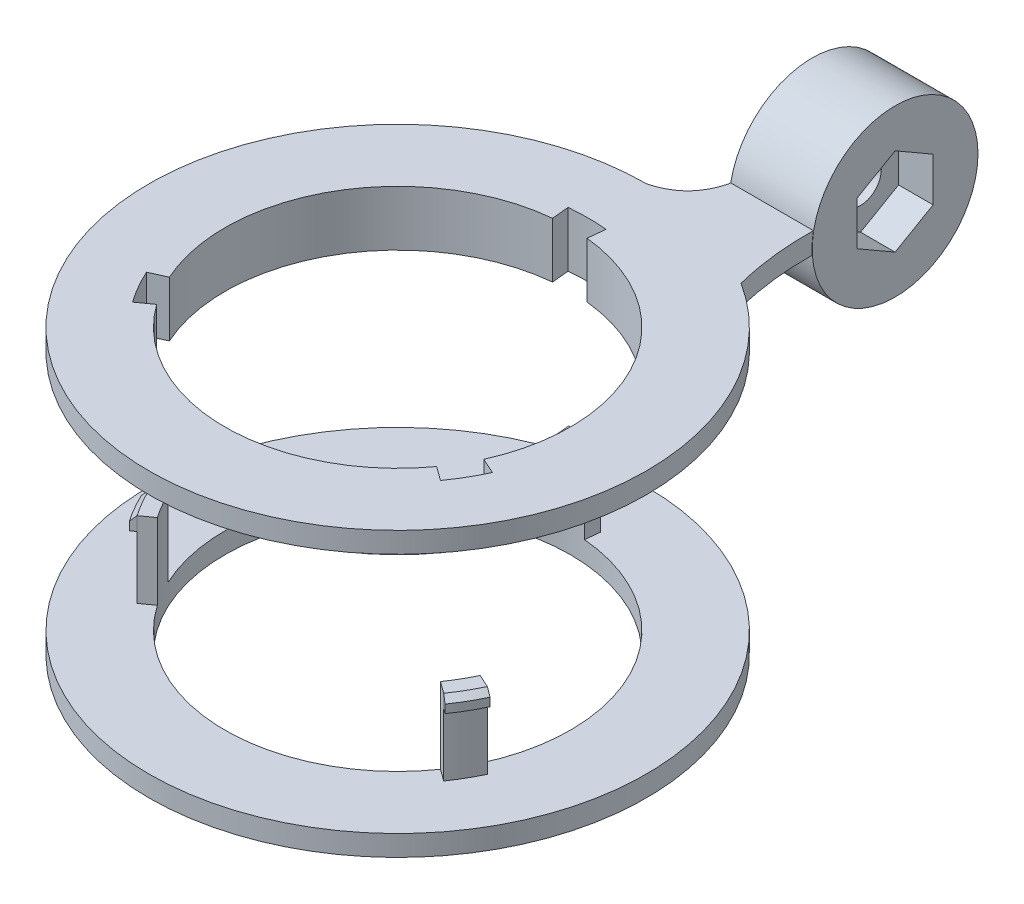
SolidWorks part; units mm, degrees
ref_plane "Plano frontal" through (0, 0, 0) normal (0, 0, 1) x (1, 0, 0)
ref_plane "Plano superior" through (0, 0, 0) normal (0, 1, 0) x (1, 0, 0)
ref_plane "Plano direito" through (0, 0, 0) normal (1, 0, 0) x (0, 0, -1)
ref_plane "Plano24" through (10, 0, 0) normal (1, 0, 0) x (0, 0, -1)
sketch "Esboço120" plane through (10, 0, 0) normal (1, 0, 0) x (0, 0, -1)
  line L6 (-78.5, 184.9522) -> (-73.5, 176.2919)
  line L7 (-78.5, 176.2919) -> (-73.5, 184.9522)
  line L8 (-80.3301, 178.1221) -> (-71.6699, 183.1221)
  line L9 (-81, 180.6221) -> (-71, 180.6221)
  line L10 (-71.6699, 178.1221) -> (-80.3301, 183.1221)
  line L11 (-76, 185.6221) -> (-76, 175.6221)
  circle A0 centre (-76, 180.6221) radius 6
  circle A2 centre (-76, 180.6221) radius 1.5
  circle A4 centre (-76, 180.6221) radius 5
  dimension "D3" = 1
extrude "Ressalto-extrusão39" add sketch "Esboço120" along normal blind 6 separate body contours A0
extrude "Corte-Extrusão-Fina1" cut sketch "Esboço120<3>" along normal blind 0.4 thin contours L9 | L10 | L6 | L11 | L7 | L8 thin type mid plane wall 0.75
sketch "Esboço120<3>" plane through (10, 0, 0) normal (1, 0, 0) x (0, 0, -1) same geometry as "Esboço120"
extrude "Corte-extrusão49" cut sketch "Esboço120<4>" along normal up to next contours A2
sketch "Esboço120<4>" plane through (10, 0, 0) normal (1, 0, 0) x (0, 0, -1) same geometry as "Esboço120"
sketch "Esboço121" plane through (16, 0, 0) normal (1, 0, 0) x (0, 0, -1)
  line L1 (-76, 183.7975) -> (-78.75, 182.2098)
  line L2 (-78.75, 182.2098) -> (-78.75, 179.0343)
  line L3 (-78.75, 179.0343) -> (-76, 177.4466)
  line L4 (-76, 177.4466) -> (-73.25, 179.0343)
  line L5 (-73.25, 179.0343) -> (-73.25, 182.2098)
  line L6 (-73.25, 182.2098) -> (-76, 183.7975)
  circle A0 centre (-76, 180.6221) radius 2.75 construction
  dimension "D1" = 5.5
extrude "Corte-extrusão50" cut sketch "Esboço121" against normal blind 2.5 contours L1 L2 L3 L4 L5 L6
ref_plane "Plao25" through (0, 180.2338, 0) normal (0, 1, 0) x (1, 0, 0)
sketch "Esboço122" plane through (0, 180.2338, 0) normal (0, 1, 0) x (1, 0, 0)
  line L0 (10, -82) -> (10, -81.5)
  line L1 (10, -82) -> (7, -82) construction
  line L2 (7, -82) -> (7, -85) construction
  line L3 (10, -81.5) -> (16, -81.5)
  line L4 (8.2693, -90.5646) -> (8.3962, -89.3211)
  line L5 (7, -85) -> (7, -93) construction
  line L6 (5.7703, -90.5606) -> (5.6474, -89.3167)
  line L7 (18.3876, -108.1548) -> (19.5264, -108.6703)
  line L8 (17.1347, -110.3169) -> (18.1482, -111.0486)
  line L9 (-3.158, -110.2846) -> (-4.1738, -111.0131)
  line L10 (-4.404, -108.1185) -> (-5.5444, -108.6303)
  circle A0 centre (7, -103) radius 18
  circle A1 centre (7, -103) radius 14.5
  circle A2 centre (7, -103) radius 15 construction
  circle A3 centre (7, -103) radius 17 construction
  circle A4 centre (7, -103) radius 12.5
  arc A5 (8.3962, -89.3211) -> (5.6474, -89.3167) centre (7, -103) ccw
  arc A6 (18.1482, -111.0486) -> (19.5264, -108.6703) centre (7, -103) ccw
  arc A7 (-5.5444, -108.6303) -> (-4.1738, -111.0131) centre (7, -103) ccw
  spline S0 degree 2 poles (10, -82) (9.3918, -84.3997) (7, -85) knots 0 0 0 1 1 1
  spline S1 degree 2 poles (16, -81.5) (15.8701, -84.6924) (16.668, -87.8168) knots 0 0 0 1 1 1
  point P3 (10, -82)
  point P35 (7, -103)
  dimension "D2" = 3
  dimension "D3" = 36
  dimension "D5" = 29
  dimension "D8" = 30
  dimension "D11" = 1.25
  dimension "D12" = 3
  dimension "D1" = 3
  dimension "D7" = 0.5
  dimension "D4" = 3.5
  dimension "D6" = 0.5
  dimension "D9" = 2
  dimension "D10" = 2
extrude "Ressalto-extrusão40" add sketch "Esboço122" along normal blind 1.5 contours S1 L3 L0 S0 A0 | A0 A1 | A1 A4 region at (12.9495, 180.2338, 83.9786) region at (11.8926, 180.2338, 86.2073) region at (-7.0899, 180.2338, 103)
extrude "Ressalto-extrusão41" add sketch "Esboço122<12>" against normal blind 2.5 contours A1 A4 region at (-7.0899, 180.2338, 103)
sketch "Esboço122<12>" plane through (0, 180.2338, 0) normal (0, 1, 0) x (1, 0, 0) same geometry as "Esboço122"
ref_plane "Plano25" through (0, 162.7338, 0) normal (0, -1, 0) x (-1, 0, 0)
sketch "Esboço123" plane through (0, 162.7338, 0) normal (0, -1, 0) x (-1, 0, 0)
  line L0 (-8.0701, -90.5459) -> (-8.1768, -89.5012)
  line L1 (-5.9695, -90.5425) -> (-5.8662, -89.4975)
  line L2 (-8.0703, -90.5443) -> (-8.1768, -89.5012) construction
  line L3 (-5.9694, -90.541) -> (-5.8662, -89.4975) construction
  line L4 (-8.2693, -90.5646) -> (-8.3962, -89.3211) construction
  line L5 (-5.7703, -90.5606) -> (-5.6474, -89.3167) construction
  line L6 (4.3206, -108.3003) -> (5.2787, -108.7303)
  line L7 (3.2732, -110.1211) -> (4.1266, -110.7331)
  line L8 (4.404, -108.1185) -> (5.5444, -108.6303) construction
  line L9 (3.158, -110.2846) -> (4.1738, -111.0131) construction
  line L10 (-17.2505, -110.1538) -> (-18.1019, -110.7685)
  line L11 (-18.3037, -108.3363) -> (-19.2604, -108.7694)
  line L12 (-8.2693, -90.5646) -> (-8.3962, -89.3211) construction
  line L13 (-5.7703, -90.5606) -> (-5.6474, -89.3167) construction
  line L14 (-17.1347, -110.3169) -> (-18.1482, -111.0486) construction
  line L15 (-18.3876, -108.1548) -> (-19.5264, -108.6703) construction
  arc A0 (4.1266, -110.7331) -> (5.2787, -108.7303) centre (-7, -103) ccw
  arc A1 (-5.8662, -89.4975) -> (-8.1768, -89.5012) centre (-7, -103) ccw
  arc A2 (4.1738, -111.0131) -> (5.5444, -108.6303) centre (-7, -103) ccw construction
  circle A3 centre (-7, -103) radius 18
  circle A4 centre (-7, -103) radius 18
  circle A5 centre (-7, -103) radius 12.5
  circle A6 centre (-7, -103) radius 12.5
  arc A7 (-5.6474, -89.3167) -> (-8.3962, -89.3211) centre (-7, -103) ccw construction
  arc A8 (-19.2604, -108.7694) -> (-18.1019, -110.7685) centre (-7, -103) ccw
  arc A9 (-19.5264, -108.6703) -> (-18.1482, -111.0486) centre (-7, -103) ccw construction
  arc A10 (-5.6474, -89.3167) -> (-8.3962, -89.3211) centre (-7, -103) ccw construction
  point P35 (-7, -103)
  dimension "D1" = 0.2
  dimension "D2" = 0
  dimension "D3" = 0
  dimension "D4" = 3
extrude "Ressalto-extrusão42" add sketch "Esboço123" along normal blind 1.5 separate body contours A4 A6 L12 A10 L13 | L13 A10 L12 A6 | A6 | A6 region at (7.0207, 162.7338, 89.9823) region at (18.2633, 162.7338, 109.5268) region at (-4.284, 162.7338, 109.4909) region at (24.4909, 162.7338, 103)
extrude "Ressalto-extrusão43" add sketch "Esboço123<3>" against normal blind 5.5 contours L11 A8 L10 A6 | A6 L7 A0 L6 | A6 L1 A1 L0 region at (7.0207, 162.7338, 89.9823) region at (18.2633, 162.7338, 109.5268) region at (-4.284, 162.7338, 109.4909)
sketch "Esboço123<3>" plane through (0, 162.7338, 0) normal (0, -1, 0) x (-1, 0, 0) same geometry as "Esboço123"
ref_plane "Plano26" through (0, 168.2338, 0) normal (0, 1, 0) x (1, 0, 0)
sketch "Esboço124" plane through (0, 168.2338, 0) normal (0, 1, 0) x (1, 0, 0)
  line L0 (18.1019, -110.7685) -> (18.4297, -110.9978)
  line L1 (19.2604, -108.7694) -> (19.6223, -108.9397)
  line L2 (8.1768, -89.5012) -> (8.2115, -89.1027)
  line L3 (5.8662, -89.4975) -> (5.8328, -89.0989)
  line L4 (-5.2787, -108.7303) -> (-5.6412, -108.8995)
  line L5 (-4.1266, -110.7331) -> (-4.4551, -110.9614)
  arc A0 (18.1019, -110.7685) -> (19.2604, -108.7694) centre (7, -103) ccw construction
  arc A1 (8.1768, -89.5012) -> (5.8662, -89.4975) centre (7, -103) ccw construction
  arc A2 (-5.2787, -108.7303) -> (-4.1266, -110.7331) centre (7, -103) ccw construction
  arc A3 (18.1019, -110.7685) -> (19.2604, -108.7694) centre (7, -103) ccw
  arc A4 (8.1768, -89.5012) -> (5.8662, -89.4975) centre (7, -103) ccw
  arc A5 (-5.2787, -108.7303) -> (-4.1266, -110.7331) centre (7, -103) ccw
  arc A6 (18.4297, -110.9978) -> (19.6223, -108.9397) centre (7, -103) ccw
  arc A7 (8.2115, -89.1027) -> (5.8328, -89.0989) centre (7, -103) ccw
  arc A8 (-5.6412, -108.8995) -> (-4.4551, -110.9614) centre (7, -103) ccw
  dimension "D1" = 0.4
extrude "Ressalto-extrusão44" add sketch "Esboço124" against normal blind 1
chamfer "Chanfro1" distance 0.4 angle 45 3 edges at (19.0699, 168.2338, 109.9942) (-5.0921, 168.2338, 109.9558) (7.0222, 168.2338, 89.05)
